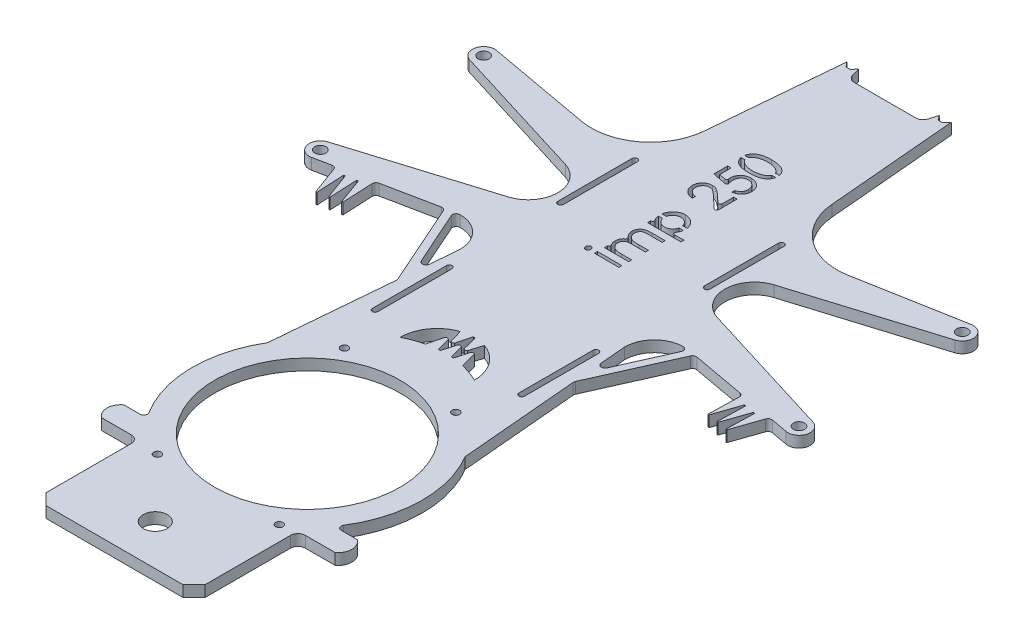
SolidWorks part; units mm, degrees
ref_plane "前视基准面" through (0, 0, 0) normal (0, 0, 1) x (1, 0, 0)
ref_plane "上视基准面" through (0, 0, 0) normal (0, 1, 0) x (1, 0, 0)
ref_plane "右视基准面" through (0, 0, 0) normal (1, 0, 0) x (0, 0, -1)
sketch "草图1" plane through (0, 0, 0) normal (0, 1, 0) x (1, 0, 0)
  line L5 (-65.3843, -19.1333) -> (-28.1418, -7.6445)
  line L6 (-63.9021, -24.9398) -> (-58.5124, -23.8437)
  line L8 (0, 0) -> (0, 91.5573) construction
  line L9 (0, 0) -> (-115.8836, 0) construction
  line L15 (0, 0) -> (0, -124.2991) construction
  line L16 (-15, -65) -> (15, -65) construction
  line L20 (-15.42, -115) -> (17.43, -115) construction
  line L21 (-28, -109.5) -> (-28, -90)
  line L22 (28, -109.5) -> (28, -90)
  line L23 (-17.5, -120) -> (17.5, -120)
  line L28 (22.5, -27) -> (22.5, 27) construction
  line L29 (-22.5, -27) -> (-22.5, 27) construction
  line L30 (28.1418, -7.6445) -> (65.3843, -19.1333)
  line L31 (28.1418, 7.6445) -> (65.3843, 19.1333)
  line L32 (-28, -90) -> (28, -90) construction
  line L33 (28, -90) -> (22.5, -27)
  line L34 (-28, -90) -> (-22.5, -27)
  line L35 (63.9635, -24.9516) -> (58.59, -23.9749)
  line L36 (0, 0) -> (104.501, 0) construction
  line L37 (-28.1418, 7.6445) -> (-65.3843, 19.1333)
  line L39 (22.5, 70) -> (22.5, 27) construction
  line L40 (-22.5, 70) -> (-22.5, 27) construction
  line L41 (31.9307, 19.129) -> (63.9635, 24.9516) construction
  line L42 (-63.9635, 24.9516) -> (-31.9307, 19.129) construction
  line L43 (-17.1562, 34.2114) -> (-14.0779, 69.4717)
  line L44 (63.9635, 24.9516) -> (35.957, 19.8608)
  line L45 (-63.9635, 24.9516) -> (-35.957, 19.8608)
  line L46 (17.1562, 34.2114) -> (14.0779, 69.4717)
  line L47 (51.4721, -37.7563) -> (54.614, -20.4713) construction
  line L48 (43.8592, -31.4611) -> (59.0133, -34.2157) construction
  line L49 (52.3717, -31.9686) -> (52.5699, -24.4476)
  line L50 (52.6668, -32.0223) -> (55.128, -24.9126)
  line L51 (-51.727, -34.6283) -> (-54.8464, -19.2902) construction
  line L52 (-52.1667, -31.7138) -> (-52.5215, -24.1986)
  line L53 (-52.4606, -31.7736) -> (-55.0694, -24.7168)
  line L54 (-55.4614, -24.7965) -> (-55.0688, -32.3041)
  line L55 (-55.3628, -32.3639) -> (-58.5124, -23.8437)
  line L56 (-52.1296, -24.1189) -> (-49.5585, -31.1834)
  line L57 (-49.2645, -31.1236) -> (-49.693, -22.05)
  line L58 (-55.3108, -33.3973) -> (-45.8391, -31.4709) construction
  line L59 (-49.693, -22.05) -> (-32.0641, -18.4647)
  line L60 (49.42, -31.4321) -> (49.6594, -22.3516)
  line L61 (49.7152, -31.4858) -> (52.1764, -24.3761)
  line L62 (55.3233, -32.5052) -> (55.5216, -24.9841)
  line L63 (55.6185, -32.5588) -> (58.59, -23.9749)
  line L64 (49.6594, -22.3516) -> (31.9307, -19.129)
  line L65 (-14.4088, 65.6811) -> (14.4088, 65.6811) construction
  line L70 (-10.8845, 69.4717) -> (-10.1819, 67.1107)
  line L75 (10.8788, 69.4717) -> (10.1832, 67.115)
  line L76 (-8.265, 65.6811) -> (8.265, 65.6811)
  line L77 (-58.5124, -23.8437) -> (-49.693, -22.05) construction
  line L78 (-55.0119, -33.3365) -> (-57.0048, -23.5371) construction
  line L79 (-49.2076, -32.156) -> (-51.2006, -22.3566) construction
  line L80 (-55.3108, -31.8666) -> (-48.2781, -30.4363) construction
  line L81 (-55.5726, -23.2458) -> (-53.8786, -31.5753) construction
  line L82 (-52.6328, -22.6479) -> (-50.9388, -30.9774) construction
  line L83 (-55.174, -25.2057) -> (-50.3177, -24.218) construction
  line L84 (49.6594, -22.3516) -> (58.59, -23.9749) construction
  line L85 (49.3846, -32.4655) -> (51.1731, -22.6267) construction
  line L86 (55.2879, -33.5385) -> (57.0763, -23.6997) construction
  line L87 (49.6529, -30.9897) -> (55.5562, -32.0627) construction
  line L88 (52.6489, -22.895) -> (50.8605, -32.7337) construction
  line L89 (55.6005, -23.4315) -> (53.8121, -33.2703) construction
  line L90 (52.2912, -24.8627) -> (55.2428, -25.3992) construction
  line L95 (-13, 68.1811) -> (-11.8, 68.1811)
  line L96 (13, 68.1811) -> (14.0779, 69.4717)
  line L97 (-13, 68.1811) -> (-14.0779, 69.4717)
  line L98 (-10.8845, 69.4717) -> (-11.8, 68.1811)
  line L99 (10.8788, 69.4717) -> (11.8, 68.1811)
  line L100 (11.8, 68.1811) -> (13, 68.1811)
  circle A0 centre (-64.5, 30) radius 1.5 construction
  circle A1 centre (64.5, 30) radius 1.5 construction
  circle A2 centre (64.5, -30) radius 1.5 construction
  circle A3 centre (-64.5, -30) radius 1.5 construction
  circle A4 centre (-64.5, 30) radius 3 construction
  circle A5 centre (64.5, 30) radius 3 construction
  circle A6 centre (64.5, -30) radius 3 construction
  circle A7 centre (-64.5, -30) radius 3 construction
  circle A10 centre (-64.5, 22) radius 1.5
  circle A11 centre (64.5, 22) radius 1.5
  circle A12 centre (64.5, -22) radius 1.5
  circle A13 centre (-64.5, -22) radius 1.5
  circle A22 centre (0, -90) radius 25
  circle A23 centre (-15, -65) radius 1
  circle A24 centre (15, -65) radius 1
  circle A25 centre (-15.42, -115) radius 1
  circle A26 centre (17.43, -115) radius 1
  arc A27 (-17.5, -120) -> (-28, -109.5) centre (-17.5, -109.5) cw
  arc A28 (17.5, -120) -> (28, -109.5) centre (17.5, -109.5) ccw
  arc A42 (63.9635, -24.9516) -> (65.3843, -19.1333) centre (64.5, -22) ccw
  arc A43 (65.3843, 19.1333) -> (63.9635, 24.9516) centre (64.5, 22) ccw
  arc A44 (28.1418, -7.6445) -> (28.1418, 7.6445) centre (30.5, 0) cw
  arc A46 (22.5, -27) -> (31.9307, -19.129) centre (30.5, -27) cw
  arc A47 (-65.3843, -19.1333) -> (-63.9021, -24.9398) centre (-64.5, -22) ccw
  arc A49 (-28.1418, -7.6445) -> (-28.1418, 7.6445) centre (-30.5, 0) ccw
  arc A50 (-22.5, -27) -> (-32.0641, -18.4647) centre (-30.4697, -26.3042) ccw
  arc A51 (-63.9635, 24.9516) -> (-65.3843, 19.1333) centre (-64.5, 22) ccw
  arc A52 (31.9307, 19.129) -> (22.5, 27) centre (30.5, 27) cw construction
  arc A53 (-31.9307, 19.129) -> (-22.5, 27) centre (-30.5, 27) ccw construction
  arc A54 (-35.957, 19.8608) -> (-17.1562, 34.2114) centre (-33.0955, 35.6029) ccw
  arc A55 (17.1562, 34.2114) -> (35.957, 19.8608) centre (33.0955, 35.6029) ccw
  arc A56 (-8.265, 65.6811) -> (-10.1819, 67.1107) centre (-8.265, 67.6811) cw
  arc A57 (10.1832, 67.115) -> (8.265, 65.6811) centre (8.265, 67.6811) cw
  arc A58 (-55.3628, -32.3639) -> (-55.0688, -32.3041) centre (-55.3108, -31.8666) ccw
  arc A59 (-52.4606, -31.7736) -> (-52.1667, -31.7138) centre (-52.4087, -31.2763) ccw
  arc A60 (-49.5585, -31.1834) -> (-49.2645, -31.1236) centre (-49.5066, -30.6861) ccw
  arc A61 (-55.4614, -24.7965) -> (-55.0694, -24.7168) centre (-55.174, -25.2057) cw
  arc A62 (-52.5215, -24.1986) -> (-52.1296, -24.1189) centre (-52.2342, -24.6078) cw
  arc A63 (49.42, -31.4321) -> (49.7152, -31.4858) centre (49.6529, -30.9897) ccw
  arc A64 (52.3717, -31.9686) -> (52.6668, -32.0223) centre (52.6045, -31.5262) ccw
  arc A65 (55.3233, -32.5052) -> (55.6185, -32.5588) centre (55.5562, -32.0627) ccw
  arc A66 (52.1764, -24.3761) -> (52.5699, -24.4476) centre (52.2912, -24.8627) cw
  arc A67 (55.128, -24.9126) -> (55.5216, -24.9841) centre (55.2428, -25.3992) cw
  point P0 (0, 0)
  point P109 (-9.7565, 65.6811)
  point P112 (9.76, 65.6811)
  dimension "D1" = 3
  dimension "D6" = 6
  dimension "D7" = 6
  dimension "D8" = 6
  dimension "D9" = 6
  dimension "D15" = 3
  dimension "D18" = 6
  dimension "D19" = 16
  dimension "D20" = 8
  dimension "D21" = 22
  dimension "D22" = 50
  dimension "D28" = 2
  dimension "D31" = 2
  dimension "D25" = 45
  dimension "D37" = 27
  dimension "D38" = 16
  dimension "D39" = 10
  dimension "D40" = 6
  dimension "D41" = 6
  dimension "D44" = 8
  dimension "D45" = 8
  dimension "D27" = 22.5
  dimension "D47" = 10.5
  dimension "D48" = 10
  dimension "D17" = 8
  dimension "D12" = 6
  dimension "D13" = 8
  dimension "D16" = 8
  dimension "D60" = 2
  dimension "D61" = 2
  dimension "D62" = 0.5
  dimension "D67" = 0.5
  dimension "D70" = 0.5
  dimension "D74" = 0.5
  dimension "D77" = 0.5
  dimension "D81" = 0.5
  dimension "D66" = 0.5
  dimension "D86" = 0.5
  dimension "D90" = 0.5
  dimension "D93" = 0.5
  dimension "D2" = 129
  dimension "D3" = 60
  dimension "D4" = 30
  dimension "D5" = 64.5
  dimension "D10" = 27
  dimension "D11" = 27
  dimension "D14" = 9.7565
  dimension "D23" = 30
  dimension "D24" = 15
  dimension "D26" = 30
  dimension "D29" = 32.85
  dimension "D30" = 2.43
  dimension "D32" = 27
  dimension "D33" = 28
  dimension "D34" = 28
  dimension "D35" = 35
  dimension "D36" = 17.5
  dimension "D42" = 45
  dimension "D43" = 22.5
  dimension "D46" = 120
  dimension "D49" = 10
  dimension "D50" = 3
  dimension "D51" = 3
  dimension "D52" = 3
  dimension "D53" = 1.5
  dimension "D54" = 10
  dimension "D55" = 3
  dimension "D56" = 1.5
  dimension "D57" = 65.6811
  dimension "D58" = 10.1819
  dimension "D59" = 10.1832
  dimension "D63" = 1.5
  dimension "D64" = 0.15
  dimension "D65" = 0.15
  dimension "D68" = 0.15
  dimension "D69" = 0.15
  dimension "D71" = 0.15
  dimension "D72" = 0.15
  dimension "D73" = 2
  dimension "D75" = 0.2
  dimension "D76" = 0.2
  dimension "D78" = 0.2
  dimension "D79" = 0.2
  dimension "D80" = 1.5
  dimension "D82" = 0.15
  dimension "D83" = 0.15
  dimension "D84" = 0.15
  dimension "D85" = 0.15
  dimension "D87" = 0.15
  dimension "D88" = 0.15
  dimension "D89" = 2
  dimension "D91" = 0.2
  dimension "D92" = 0.2
  dimension "D94" = 0.2
  dimension "D95" = 0.2
  dimension "D96" = 3.7906
  dimension "D97" = 8.265
  dimension "D98" = 3.7906
  dimension "D99" = 8.265
  dimension "D100" = 9.76
  dimension "D101" = 22.5
  dimension "D102" = 26
  dimension "D103" = 13
  dimension "D104" = 2.5
  dimension "D105" = 10.8845
  dimension "D106" = 10.8788
  dimension "D107" = 1.2
  dimension "D108" = 1.2
extrude "凸台-拉伸1" add sketch "草图1" along normal blind 3
sketch "草图2" plane through (0, 0, 0) normal (0, -1, 0) x (1, 0, 0)
  line L0 (0, 133.3282) -> (0, -97.043) construction
  line L1 (-19.75, 2) -> (-19.75, -18) construction
  line L2 (-19, 2) -> (-19, -18)
  line L3 (-20.5, 2) -> (-20.5, -18)
  line L4 (19.75, 2) -> (19.75, -18) construction
  line L5 (20.5, 2) -> (20.5, -18)
  line L6 (19, 2) -> (19, -18)
  line L7 (0, 0) -> (56.7659, 0) construction
  line L8 (-19.75, 52) -> (-19.75, 32) construction
  line L9 (-19, 52) -> (-19, 32)
  line L10 (-20.5, 52) -> (-20.5, 32)
  line L11 (19.75, 52) -> (19.75, 32) construction
  line L12 (20.5, 52) -> (20.5, 32)
  line L13 (19, 52) -> (19, 32)
  arc A0 (-19, 2) -> (-20.5, 2) centre (-19.75, 2) ccw
  arc A1 (-20.5, -18) -> (-19, -18) centre (-19.75, -18) ccw
  arc A2 (20.5, 2) -> (19, 2) centre (19.75, 2) ccw
  arc A3 (19, -18) -> (20.5, -18) centre (19.75, -18) ccw
  arc A4 (-19, 52) -> (-20.5, 52) centre (-19.75, 52) ccw
  arc A5 (-20.5, 32) -> (-19, 32) centre (-19.75, 32) ccw
  arc A6 (20.5, 52) -> (19, 52) centre (19.75, 52) ccw
  arc A7 (19, 32) -> (20.5, 32) centre (19.75, 32) ccw
  arc A8 (-10, 55) -> (10, 55) centre (0, 55) ccw
  arc A9 (-10, 55) -> (10, 55) centre (0, 74.5959) ccw
  point P5 (-19.75, -8)
  point P10 (19.75, -8)
  point P19 (-19.75, 42)
  point P26 (19.75, 42)
  dimension "D6" = 42
  dimension "D8" = 10
  dimension "D9" = 22
  dimension "D1" = 1.5
  dimension "D2" = 20
  dimension "D3" = 19
  dimension "D4" = 19
  dimension "D5" = 8
  dimension "D7" = 55
  dimension "D10" = 10
extrude "切除-拉伸1" cut sketch "草图2" against normal blind 3
sketch "草图3" plane through (0, 0, 0) normal (0, -1, 0) x (1, 0, 0)
  line L0 (0, 67.5428) -> (0, 43.0807) construction
  line L1 (-3.5, 60.2388) -> (-3.5, 43.3854) construction
  line L2 (3.5, 60.0167) -> (3.5, 43.3854) construction
  line L3 (-1.5, 52.6471) -> (-0.4454, 48.96)
  line L4 (0.4454, 48.96) -> (1.5, 52.6471)
  line L5 (-5.2946, 47.5) -> (4.5072, 47.5) construction
  line L6 (-3.0546, 48.96) -> (-2, 52.687)
  line L7 (-5, 53.1716) -> (-3.9454, 48.96)
  line L8 (3.0546, 48.96) -> (2, 52.687)
  line L9 (3.9454, 48.96) -> (5, 53.1716)
  line L10 (-5.8174, 50.5) -> (6.3675, 50.5) construction
  line L11 (-5.8021, 45) -> (6.2608, 45) construction
  line L12 (-1.75, 52.0659) -> (-1.75, 44.2103) construction
  line L13 (1.75, 52.0659) -> (1.75, 43.5429) construction
  line L14 (-1.3046, 49.04) -> (-0.25, 45.0031)
  line L15 (-2.1906, 49.0439) -> (-3.25, 45.5429)
  line L16 (1.3046, 49.04) -> (0.25, 45.0031)
  line L17 (2.1954, 49.04) -> (3.25, 45.5429)
  line L18 (-5, 53.1716) -> (-5, 54.1716)
  line L19 (-5, 54.1716) -> (5, 54.1716)
  line L20 (5, 54.1716) -> (5, 53.1716)
  line L21 (-2, 52.687) -> (-2, 53.687)
  line L22 (-2, 53.687) -> (-1.5, 53.687)
  line L23 (-1.5, 53.687) -> (-1.5, 52.6471)
  line L24 (1.5, 52.6471) -> (1.5, 53.687)
  line L25 (1.5, 53.687) -> (2, 53.687)
  line L26 (2, 53.687) -> (2, 52.687)
  line L27 (-3.25, 45.5429) -> (-3.25, 43.5429)
  line L28 (-3.25, 43.5429) -> (3.25, 43.5429)
  line L29 (3.25, 43.5429) -> (3.25, 45.5429)
  line L30 (-0.25, 45.0031) -> (-0.25, 44.0031)
  line L31 (-0.25, 44.0031) -> (0.25, 44.0031)
  line L32 (0.25, 44.0031) -> (0.25, 45.0031)
  arc A0 (-10, 55) -> (10, 55) centre (0, 74.5959) ccw construction
  arc A1 (-10, 55) -> (10, 55) centre (0, 74.5959) ccw construction
  arc A2 (-10, 55) -> (10, 55) centre (0, 55) ccw construction
  arc A3 (-10, 55) -> (10, 55) centre (0, 55) ccw construction
  arc A4 (-3.9454, 48.96) -> (-3.0546, 48.96) centre (-3.5, 49.5) ccw
  arc A5 (0.4454, 48.96) -> (-0.4454, 48.96) centre (0, 49.5) cw
  arc A6 (3.9454, 48.96) -> (3.0546, 48.96) centre (3.5, 49.5) cw
  arc A7 (-2.1906, 49.0439) -> (-1.3046, 49.04) centre (-1.75, 48.5) cw
  arc A8 (1.3046, 49.04) -> (2.1954, 49.04) centre (1.75, 48.5) cw
  dimension "D21" = 0.7
  dimension "D25" = 0.7
  dimension "D26" = 0.7
  dimension "D28" = 0.7
  dimension "D33" = 0.7
  dimension "D1" = 3.5
  dimension "D2" = 3.5
  dimension "D3" = 7.5
  dimension "D4" = 3
  dimension "D5" = 1.5
  dimension "D6" = 1.5
  dimension "D7" = 1.5
  dimension "D8" = 3
  dimension "D9" = 1.5
  dimension "D10" = 5.5
  dimension "D11" = 1.75
  dimension "D12" = 3.5
  dimension "D13" = 1.5
  dimension "D14" = 1.5
  dimension "D15" = 1.5
  dimension "D16" = 1.5
  dimension "D17" = 1
  dimension "D18" = 1
  dimension "D19" = 1
  dimension "D20" = 2
  dimension "D22" = 2
  dimension "D23" = 1.46
  dimension "D24" = 1.46
  dimension "D27" = 2
  dimension "D29" = 1.4561
  dimension "D30" = 1.46
  dimension "D31" = 2
  dimension "D32" = 1.46
  dimension "D34" = 1.46
extrude "凸台-拉伸2" add sketch "草图3" against normal blind 3
sketch "草图4" plane through (0, 0, 0) normal (0, -1, 0) x (1, 0, 0)
  line L0 (0, 0) -> (0, 140.5969) construction
  line L1 (-28, 108) -> (-21.4476, 108)
  line L2 (-17.5, 120) -> (17.5, 120) construction
  line L3 (-28, 90) -> (28, 90) construction
  line L4 (-28, 90) -> (-28, 109.5) construction
  line L5 (28, 109.5) -> (28, 90) construction
  line L6 (-21.4476, 114) -> (-21.4476, 119.2297)
  line L7 (21.4476, 119.2297) -> (21.4476, 114)
  line L8 (21.4476, 108) -> (28, 108)
  line L9 (-21.4476, 114) -> (-26.9868, 114)
  line L10 (21.4476, 114) -> (26.9868, 114)
  line L11 (-28, 108) -> (-28, 90)
  line L12 (28, 108) -> (28, 90)
  circle A0 centre (0, 90) radius 25 construction
  circle A1 centre (0, 90) radius 25 construction
  arc A2 (-21.4476, 108) -> (-28, 90) centre (0, 90) ccw
  arc A3 (28, 90) -> (21.4476, 108) centre (0, 90) ccw
  arc A4 (-17.5, 120) -> (-28, 109.5) centre (-17.5, 109.5) ccw construction
  arc A5 (28, 109.5) -> (17.5, 120) centre (17.5, 109.5) ccw construction
  arc A6 (-21.4476, 119.2297) -> (-26.9868, 114) centre (-17.5, 109.5) ccw
  arc A7 (26.9868, 114) -> (21.4476, 119.2297) centre (17.5, 109.5) ccw
  dimension "D1" = 12
  dimension "D4" = 6
  dimension "D5" = 6
extrude "切除-拉伸2" cut sketch "草图4" against normal blind 3
sketch "草图6" plane through (0, 0, 0) normal (0, -1, 0) x (1, 0, 0)
  line L0 (-21.4476, 119.2297) -> (-21.4476, 139)
  line L1 (-18.4476, 142) -> (18.4476, 142)
  line L2 (21.4476, 139) -> (21.4476, 119.2297)
  line L3 (-17.5, 120) -> (17.5, 120) construction
  line L4 (0, 0) -> (0, 166.5632) construction
  line L5 (-21.4476, 131) -> (21.4476, 131) construction
  line L6 (-21.4476, 139) -> (-18.4476, 142)
  line L7 (18.4476, 142) -> (21.4476, 139)
  line L8 (-21.4476, 119.2297) -> (21.4476, 119.2297)
  circle A0 centre (0, 131) radius 3.25
  point P1 (-21.4476, 142)
  point P4 (21.4476, 142)
  dimension "D3" = 6.5
  dimension "D1" = 22
  dimension "D2" = 11
extrude "凸台-拉伸3" add sketch "草图6" against normal blind 3
sketch "草图7" plane through (0, 0, 0) normal (0, -1, 0) x (1, 0, 0)
  line L0 (-21.4476, 108) -> (-28, 108) construction
  line L1 (-21.4476, 108) -> (-28, 108) construction
  line L2 (28, 108) -> (21.4476, 108) construction
  line L3 (28, 108) -> (21.4476, 108) construction
  line L4 (-22.5, 27) -> (-28, 90) construction
  line L5 (-26.6119, 74.1001) -> (-28, 90)
  line L6 (28, 90) -> (22.5, 27) construction
  line L7 (28, 90) -> (26.6119, 74.1001)
  line L8 (-25.2389, 108) -> (-21.4476, 108)
  line L9 (21.4476, 108) -> (25.2389, 108)
  circle A0 centre (0, 90) radius 25 construction
  circle A1 centre (0, 90) radius 25 construction
  arc A2 (-25.2389, 108) -> (-26.6119, 74.1001) centre (0, 90) ccw
  arc A3 (26.6119, 74.1001) -> (25.2389, 108) centre (0, 90) ccw
  arc A4 (-21.4476, 108) -> (-28, 90) centre (0, 90) ccw construction
  arc A5 (-21.4476, 108) -> (-28, 90) centre (0, 90) ccw
  arc A6 (28, 90) -> (21.4476, 108) centre (0, 90) ccw construction
  arc A7 (28, 90) -> (21.4476, 108) centre (0, 90) ccw
  dimension "D1" = 62
extrude "凸台-拉伸4" add sketch "草图7" against normal blind 3
sketch "草图8" plane through (0, 3, 0) normal (0, 1, 0) x (1, 0, 0)
  line L0 (3.1484, -10) -> (3.1484, 45.0133) construction
  text T0 "imp 250" font "Century Gothic" height 9
  dimension "D1" = 4.5
  dimension "D2" = 10
extrude "切除-拉伸3" cut sketch "草图8" against normal blind 10 body kept at (-63.9021, 0, 24.9398)
sketch "草图9" plane through (0, 3, 0) normal (0, 1, 0) x (1, 0, 0)
  line L0 (2.0356, 9.1058) -> (3.5183, 9.1058)
  line L1 (-0.1581, 8.6058) -> (3.2638, 8.6058) construction
  line L2 (2.0356, 8.1058) -> (3.5183, 8.1058)
  line L3 (-0.1581, 8.6058) -> (-0.1581, 12.0385) construction
  line L4 (-2.3518, 8.1058) -> (-3.8345, 8.1058)
  line L5 (-2.3518, 9.1058) -> (-3.8345, 9.1058)
  line L6 (-3.8345, 9.1058) -> (-3.8345, 8.1058)
  line L7 (3.5183, 9.1058) -> (3.5183, 8.1058)
  line L8 (-1.348, 36.5) -> (-1.348, 30.3846) construction
  line L9 (-6.0824, 33.3936) -> (3.3792, 33.3936) construction
  line L10 (2.2705, 33.8936) -> (4.4204, 33.8936)
  line L11 (4.4204, 33.8936) -> (4.4204, 32.8936)
  line L12 (4.4204, 32.8936) -> (2.2705, 32.8936)
  line L13 (-7.1164, 33.8936) -> (-7.1164, 32.8936)
  line L14 (-7.1164, 32.8936) -> (-4.9665, 32.8936)
  line L15 (-4.9665, 33.8936) -> (-7.1164, 33.8936)
  arc A0 (2.0356, 9.1058) -> (-2.3518, 9.1058) centre (-0.1581, 8.6058) ccw
  arc A1 (-2.3518, 8.1058) -> (2.0356, 8.1058) centre (-0.1581, 8.6058) ccw
  ellipse E0 centre (-1.348, 33.3936) end of major axis (2.382, 33.3936) minor radius 2.06 (2.2705, 33.8936) -> (-4.9665, 33.8936) ccw
  ellipse E1 centre (-1.348, 33.3936) end of major axis (2.382, 33.3936) minor radius 2.06 (-4.9665, 32.8936) -> (2.2705, 32.8936) ccw
  spline S0 degree 3 poles (119.9759, 2008.3244) (-17.7351, -17.5347) (-7.5163, 13.1276) (0.527, 11.9809) (0.8523, 11.9039) (1.1641, 11.7931) (1.4624, 11.6501) (1.7468, 11.476) (2.0173, 11.2705) (2.2702, 11.0358) (2.5031, 10.7811) (2.7069, 10.5088) (2.878, 10.2232) (3.0209, 9.9258) (3.1287, 9.6139) (3.2064, 9.2891) (4.3488, 1.2408) (-26.1344, -8.9183) (1999.6881, 125.4925) knots -4.320217 -4.320217 -4.320217 -4.320217 0.064921 0.128034 0.189574 0.25058 0.311733 0.37325 0.435763 0.500346 0.564949 0.627528 0.689157 0.749865 0.81076 0.8723 0.935413 5.32242 5.32242 5.32242 5.32242 only from (-0.1581, 12.0385) to (3.2638, 8.6058) construction
  spline S1 degree 3 poles (-2000.4655, 116.8053) (24.955, -9.3137) (-4.5971, 0.9377) (-3.4887, 9.2675) (-3.4112, 9.5946) (-3.2996, 9.9072) (-3.1617, 10.2087) (-2.9875, 10.4947) (-2.7859, 10.7696) (-2.5539, 11.0266) (-2.3028, 11.264) (-2.0328, 11.4693) (-1.7526, 11.6464) (-1.4579, 11.7895) (-1.1511, 11.9017) (-0.8309, 11.9814) (7.1294, 13.118) (17.1817, -17.21) (-116.7184, 2008.5336) knots -4.485893 -4.485893 -4.485893 -4.485893 0.065081 0.128636 0.190653 0.252125 0.313446 0.375227 0.438498 0.503285 0.56801 0.630879 0.692154 0.752552 0.813191 0.873985 0.936258 5.28658 5.28658 5.28658 5.28658 only from (-3.5439, 8.5805) to (-0.1581, 12.0385) construction
  spline S2 degree 3 poles (-0.1581, 12.0385) (-0.0414, 12.0353) (0.1889, 12.0291) (0.527, 11.9809) (0.8523, 11.9039) (1.1641, 11.7931) (1.4624, 11.6501) (1.7468, 11.476) (2.0173, 11.2705) (2.2702, 11.0358) (2.5031, 10.7811) (2.7069, 10.5088) (2.878, 10.2232) (3.0209, 9.9258) (3.1287, 9.6139) (3.2064, 9.2891) (3.2543, 8.9515) (3.2606, 8.7219) (3.2638, 8.6058) knots 0 0 0 0 0.064921 0.128034 0.189574 0.25058 0.311733 0.37325 0.435763 0.500346 0.564949 0.627528 0.689157 0.749865 0.81076 0.8723 0.935413 1 1 1 1 construction
  spline S3 degree 3 poles (-3.5439, 8.5805) (-3.5405, 8.6973) (-3.5339, 8.928) (-3.4887, 9.2675) (-3.4112, 9.5946) (-3.2996, 9.9072) (-3.1617, 10.2087) (-2.9875, 10.4947) (-2.7859, 10.7696) (-2.5539, 11.0266) (-2.3028, 11.264) (-2.0328, 11.4693) (-1.7526, 11.6464) (-1.4579, 11.7895) (-1.1511, 11.9017) (-0.8309, 11.9814) (-0.4985, 12.0289) (-0.2724, 12.0352) (-0.1581, 12.0385) knots 0 0 0 0 0.065081 0.128636 0.190653 0.252125 0.313446 0.375227 0.438498 0.503285 0.56801 0.630879 0.692154 0.752552 0.813191 0.873985 0.936258 1 1 1 1 construction
  spline S4 degree 3 poles (2000.9321, -62.7776) (-20.7631, 46.3576) (4.0588, 38.9745) (3.3511, 32.9753) (3.3118, 32.774) (3.2567, 32.5778) (3.1893, 32.3857) (3.1015, 32.2003) (3.0004, 32.0196) (2.8852, 31.844) (2.7532, 31.6768) (2.6072, 31.5171) (2.4436, 31.369) (2.2648, 31.2304) (2.0713, 31.1005) (1.8631, 30.9793) (1.6397, 30.8679) (1.3997, 30.7659) (1.1396, 30.6755) (0.8569, 30.5959) (0.5488, 30.5324) (0.2167, 30.4786) (-0.1399, 30.4354) (-0.5213, 30.4053) (-13.6016, 29.8171) (-27.045, 52.7837) (2.2151, -1969.4059) knots -2.77282 -2.77282 -2.77282 -2.77282 0.033789 0.066625 0.099289 0.131367 0.163592 0.196113 0.228912 0.26217 0.296004 0.330232 0.365076 0.400968 0.437877 0.475966 0.51564 0.556675 0.600028 0.64669 0.696419 0.749772 0.80685 0.86743 0.931884 7.040457 7.040457 7.040457 7.040457 only from (3.3792, 33.3936) to (-1.348, 30.3846) construction
  spline S5 degree 3 poles (-3.9881, -1969.4307) (24.522, 52.8132) (10.9932, 29.8172) (-2.1808, 30.4053) (-2.5638, 30.4356) (-2.9216, 30.4771) (-3.2542, 30.5276) (-3.5609, 30.595) (-3.8428, 30.6717) (-4.1011, 30.7605) (-4.3392, 30.8608) (-4.5614, 30.9699) (-4.7675, 31.0922) (-4.9607, 31.2207) (-5.138, 31.3605) (-5.3015, 31.5086) (-5.4498, 31.6678) (-5.5829, 31.8368) (-5.6997, 32.0142) (-5.8032, 32.1954) (-5.8885, 32.3834) (-5.9582, 32.5759) (-6.0152, 32.7732) (-6.0543, 32.9753) (-6.7635, 38.9629) (18.1061, 46.3619) (-2003.5332, -64.7288) knots -6.074768 -6.074768 -6.074768 -6.074768 0.06859 0.133236 0.194298 0.251261 0.304491 0.354209 0.400451 0.443378 0.483979 0.523213 0.561001 0.597856 0.633471 0.668265 0.702638 0.736825 0.77043 0.803572 0.835925 0.86847 0.900854 0.933471 0.96626 3.763599 3.763599 3.763599 3.763599 only from (-1.348, 30.3846) to (-6.0824, 33.3936) construction
  spline S6 degree 3 poles (-9.3463, 2036.2829) (-28.5031, 16.4186) (-14.4158, 37.0679) (-0.5494, 36.4783) (-0.1791, 36.4447) (0.1695, 36.4032) (0.4968, 36.3451) (0.8024, 36.275) (1.0874, 36.1952) (1.3498, 36.0984) (1.5939, 35.9918) (1.822, 35.876) (2.0357, 35.7518) (2.2337, 35.6172) (2.4156, 35.4719) (2.5814, 35.3164) (2.7337, 35.1527) (2.8685, 34.9786) (2.99, 34.7994) (3.0925, 34.6121) (3.1813, 34.4215) (3.2539, 34.2256) (3.3101, 34.0248) (3.3488, 33.8184) (4.0986, 28.0102) (-21.8101, 20.5634) (2000.0942, 144.4182) knots -6.373339 -6.373339 -6.373339 -6.373339 0.065069 0.127067 0.185532 0.240785 0.293004 0.342556 0.388955 0.432815 0.474671 0.514821 0.553655 0.591479 0.627861 0.663639 0.698823 0.733433 0.76763 0.801074 0.83425 0.86697 0.899712 0.932696 0.966173 3.663842 3.663842 3.663842 3.663842 only from (-1.348, 36.5) to (3.3792, 33.3936) construction
  spline S7 degree 3 poles (-2002.3285, 154.2545) (19.4061, 20.5491) (-6.8121, 28.0786) (-6.0516, 33.8176) (-6.0157, 34.0239) (-5.9581, 34.2233) (-5.8892, 34.4197) (-5.7983, 34.6083) (-5.6994, 34.7956) (-5.5788, 34.9731) (-5.4455, 35.1462) (-5.2941, 35.3085) (-5.129, 35.4641) (-4.9462, 35.6071) (-4.7488, 35.7436) (-4.535, 35.8686) (-4.3053, 35.9845) (-4.0607, 36.0936) (-3.7948, 36.189) (-3.5091, 36.2738) (-3.2012, 36.3434) (-2.8726, 36.4008) (-2.5219, 36.4455) (-2.1496, 36.4779) (11.5517, 37.0747) (25.5551, 16.0614) (-0.9014, 2036.3513) knots -2.630094 -2.630094 -2.630094 -2.630094 0.033788 0.067226 0.099841 0.132545 0.16513 0.198011 0.23128 0.265044 0.299216 0.334359 0.369695 0.406258 0.443804 0.482982 0.523085 0.565267 0.609343 0.656393 0.705887 0.758326 0.813833 0.872795 0.934723 7.287874 7.287874 7.287874 7.287874 only from (-6.0824, 33.3936) to (-1.348, 36.5) construction
  spline S8 degree 3 poles (3.3792, 33.3936) (3.378, 33.3226) (3.3756, 33.1827) (3.3511, 32.9753) (3.3118, 32.774) (3.2567, 32.5778) (3.1893, 32.3857) (3.1015, 32.2003) (3.0004, 32.0196) (2.8852, 31.844) (2.7532, 31.6768) (2.6072, 31.5171) (2.4436, 31.369) (2.2648, 31.2304) (2.0713, 31.1005) (1.8631, 30.9793) (1.6397, 30.8679) (1.3997, 30.7659) (1.1396, 30.6755) (0.8569, 30.5959) (0.5488, 30.5324) (0.2167, 30.4786) (-0.1399, 30.4354) (-0.5213, 30.4053) (-0.9265, 30.3871) (-1.205, 30.3855) (-1.348, 30.3846) knots 0 0 0 0 0.033789 0.066625 0.099289 0.131367 0.163592 0.196113 0.228912 0.26217 0.296004 0.330232 0.365076 0.400968 0.437877 0.475966 0.51564 0.556675 0.600028 0.64669 0.696419 0.749772 0.80685 0.86743 0.931884 1 1 1 1 construction
  spline S9 degree 3 poles (-1.348, 30.3846) (-1.4923, 30.3855) (-1.7725, 30.3871) (-2.1808, 30.4053) (-2.5638, 30.4356) (-2.9216, 30.4771) (-3.2542, 30.5276) (-3.5609, 30.595) (-3.8428, 30.6717) (-4.1011, 30.7605) (-4.3392, 30.8608) (-4.5614, 30.9699) (-4.7675, 31.0922) (-4.9607, 31.2207) (-5.138, 31.3605) (-5.3015, 31.5086) (-5.4498, 31.6678) (-5.5829, 31.8368) (-5.6997, 32.0142) (-5.8032, 32.1954) (-5.8885, 32.3834) (-5.9582, 32.5759) (-6.0152, 32.7732) (-6.0543, 32.9753) (-6.0788, 33.1827) (-6.0812, 33.3226) (-6.0824, 33.3936) knots 0 0 0 0 0.06859 0.133236 0.194298 0.251261 0.304491 0.354209 0.400451 0.443378 0.483979 0.523213 0.561001 0.597856 0.633471 0.668265 0.702638 0.736825 0.77043 0.803572 0.835925 0.86847 0.900854 0.933471 0.96626 1 1 1 1 construction
  spline S10 degree 3 poles (-1.348, 36.5) (-1.2104, 36.4983) (-0.9416, 36.495) (-0.5494, 36.4783) (-0.1791, 36.4447) (0.1695, 36.4032) (0.4968, 36.3451) (0.8024, 36.275) (1.0874, 36.1952) (1.3498, 36.0984) (1.5939, 35.9918) (1.822, 35.876) (2.0357, 35.7518) (2.2337, 35.6172) (2.4156, 35.4719) (2.5814, 35.3164) (2.7337, 35.1527) (2.8685, 34.9786) (2.99, 34.7994) (3.0925, 34.6121) (3.1813, 34.4215) (3.2539, 34.2256) (3.3101, 34.0248) (3.3488, 33.8184) (3.376, 33.6077) (3.3781, 33.4652) (3.3792, 33.3936) knots 0 0 0 0 0.065069 0.127067 0.185532 0.240785 0.293004 0.342556 0.388955 0.432815 0.474671 0.514821 0.553655 0.591479 0.627861 0.663639 0.698823 0.733433 0.76763 0.801074 0.83425 0.86697 0.899712 0.932696 0.966173 1 1 1 1 construction
  spline S11 degree 3 poles (-6.0824, 33.3936) (-6.0814, 33.4652) (-6.0794, 33.6077) (-6.0516, 33.8176) (-6.0157, 34.0239) (-5.9581, 34.2233) (-5.8892, 34.4197) (-5.7983, 34.6083) (-5.6994, 34.7956) (-5.5788, 34.9731) (-5.4455, 35.1462) (-5.2941, 35.3085) (-5.129, 35.4641) (-4.9462, 35.6071) (-4.7488, 35.7436) (-4.535, 35.8686) (-4.3053, 35.9845) (-4.0607, 36.0936) (-3.7948, 36.189) (-3.5091, 36.2738) (-3.2012, 36.3434) (-2.8726, 36.4008) (-2.5219, 36.4455) (-2.1496, 36.4779) (-1.7556, 36.4951) (-1.4862, 36.4983) (-1.348, 36.5) knots 0 0 0 0 0.033788 0.067226 0.099841 0.132545 0.16513 0.198011 0.23128 0.265044 0.299216 0.334359 0.369695 0.406258 0.443804 0.482982 0.523085 0.565267 0.609343 0.656393 0.705887 0.758326 0.813833 0.872795 0.934723 1 1 1 1 construction
  dimension "D1" = 4.5
  dimension "D2" = 8.6058
  dimension "D3" = 0.1581
  dimension "D4" = 0.5
  dimension "D5" = 1.4826
  dimension "D6" = 7.46
  dimension "D7" = 9.4615
  dimension "D8" = 6.1154
  dimension "D9" = 4.12
  dimension "D10" = 0.5
  dimension "D11" = 0.5
  dimension "D12" = 2.1499
extrude "凸台-拉伸5" add sketch "草图9" against normal blind 3
sketch "草图10" plane through (0, 0, 0) normal (0, -1, 0) x (1, 0, 0)
  line L0 (-26.9868, 114) -> (-31.4868, 114)
  line L2 (-31.4868, 108) -> (-26.9868, 108)
  line L3 (-26.9868, 108) -> (-26.9868, 114)
  line L4 (-25.2389, 108) -> (-28, 108) construction
  line L5 (0, 0) -> (0, 153.1529) construction
  line L10 (26.9868, 108) -> (26.9868, 114)
  line L11 (31.4868, 108) -> (26.9868, 108)
  line L12 (26.9868, 114) -> (31.4868, 114)
  arc A0 (-31.4868, 114) -> (-31.4868, 108) centre (-29.2368, 111) ccw
  arc A1 (31.4868, 114) -> (31.4868, 108) centre (29.2368, 111) cw
  dimension "D1" = 3.75
  dimension "D2" = 4.5
  dimension "D3" = 4.5
extrude "凸台-拉伸6" add sketch "草图10" against normal blind 3
fillet "圆角2" radius 2 1 edges at (-21.4476, 1.5, 114)
fillet "圆角3" radius 2 1 edges at (21.4476, 1.5, 114)
fillet "圆角4" radius 1 1 edges at (-25.2389, 1.5, 108)
fillet "圆角5" radius 1 1 edges at (25.2389, 1.5, 108)
sketch "草图11" plane through (0, 0, 0) normal (0, -1, 0) x (1, 0, 0)
  line L0 (-22.5, 27) -> (-26.6119, 74.1001) construction
  line L1 (-22.5, 27) -> (-26.6119, 74.1001) construction
  line L2 (-49.693, 22.05) -> (-32.0641, 18.4647) construction
  line L3 (-49.693, 22.05) -> (-32.0641, 18.4647) construction
  line L4 (-32.0641, 18.4647) -> (-23.4449, 37.8236)
  line L5 (-32.0641, 18.4647) -> (30.3166, 18.4647) construction
  line L6 (-23.8038, 41.9347) -> (-34.0716, 18.873)
  line L7 (-23.8038, 41.9347) -> (-23.4449, 37.8236)
  line L8 (-34.0716, 18.873) -> (-32.0641, 18.4647)
  line L9 (0, 0) -> (0, 75.6123) construction
  line L10 (34.0716, 18.873) -> (32.0641, 18.4647)
  line L11 (23.8038, 41.9347) -> (23.4449, 37.8236)
  line L12 (23.8038, 41.9347) -> (34.0716, 18.873)
  line L13 (32.0641, 18.4647) -> (23.4449, 37.8236)
  dimension "D1" = 66
  dimension "D2" = 2
extrude "凸台-拉伸7" add sketch "草图11" against normal blind 3
fillet "圆角6" radius 1 1 edges at (23.8038, 1.5, 41.9347)
fillet "圆角7" radius 1 1 edges at (23.4449, 1.5, 37.8236)
fillet "圆角9" radius 1 1 edges at (31.7799, 1.5, 19.103)
fillet "圆角10" radius 1 1 edges at (33.8058, 1.5, 19.4698)
fillet "圆角11" radius 1 1 edges at (-23.8038, 1.5, 41.9347)
fillet "圆角12" radius 1 1 edges at (-34.0716, 1.5, 18.873)
fillet "圆角13" radius 1 1 edges at (-23.4449, 1.5, 37.8236)
fillet "圆角14" radius 1 1 edges at (-32.0641, 1.5, 18.4647)
fillet "圆角15" radius 1 1 edges at (58.59, 1.5, 23.9749)
fillet "圆角16" radius 1 1 edges at (49.6594, 1.5, 22.3516)
fillet "圆角18" radius 1 1 edges at (-58.5124, 1.5, 23.8437)
fillet "圆角19" radius 1 1 edges at (-49.693, 1.5, 22.05)
fillet "圆角22" radius 0.5 1 edges at (-2.2855, 1.5, 5.7308)
fillet "圆角23" radius 0.5 1 edges at (-1.9556, 1.5, 1.3696)
fillet "圆角24" radius 0.5 1 edges at (-2.2116, 1.5, -5.9231)
fillet "圆角25" radius 0.5 1 edges at (1.9567, 1.5, -5.9231)
fillet "圆角26" radius 0.5 1 edges at (2.2253, 1.5, -18.4657)
fillet "圆角27" radius 0.5 1 edges at (3.1484, 1.5, -16.5385)
fillet "圆角28" radius 0.5 1 edges at (-1.3516, 1.5, -24.5)
fillet "圆角29" radius 0.5 1 edges at (-2.5613, 1.5, -25.5691)
